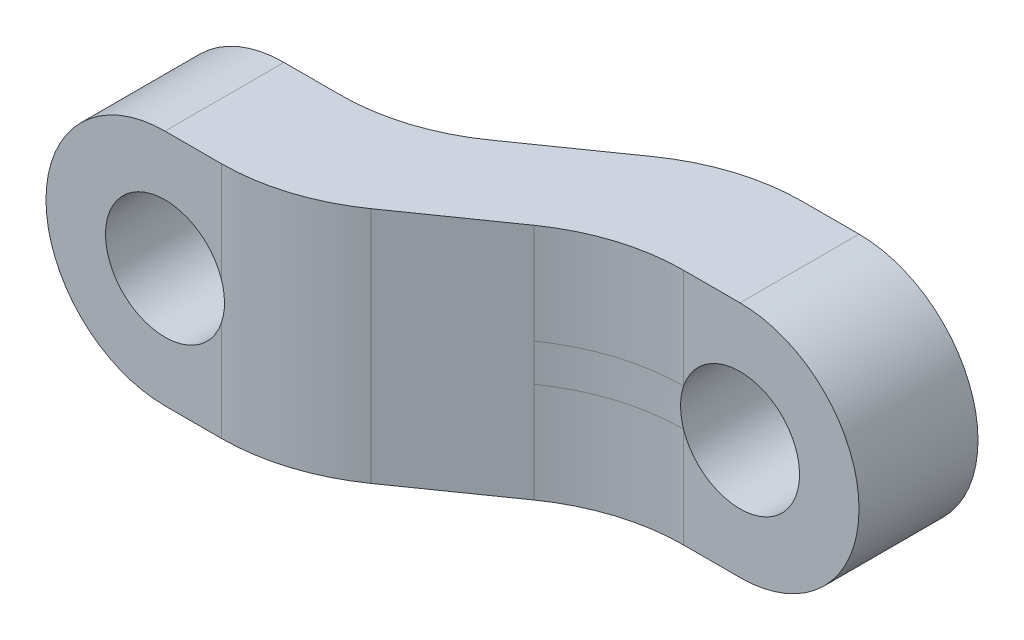
SolidWorks part; units mm, degrees
ref_plane "Front Plane" through (0, 0, 0) normal (0, 0, 1) x (1, 0, 0)
ref_plane "Top Plane" through (0, 0, 0) normal (0, 1, 0) x (1, 0, 0)
ref_plane "Right Plane" through (0, 0, 0) normal (1, 0, 0) x (0, 0, -1)
sketch "Sketch2" plane through (0, 0, 0) normal (0, 0, 1) x (1, 0, 0)
  line L1 (-3, -3) -> (3, -3)
  line L2 (-3, -3) -> (-3, 3)
  line L3 (-3, 3) -> (3, 3)
  line L4 (3, -3) -> (3, 3)
  line L5 (-3, -3) -> (3, 3) construction
  line L6 (-3, 3) -> (3, -3) construction
  circle A0 centre (0, 0) radius 1.5
  circle A1 centre (0, 0) radius 3
  dimension "D1" = 3
  dimension "D2" = 6
  dimension "D3" = 6
sketch "Sketch3" plane through (0, 0, 0) normal (0, 1, 0) x (1, 0, 0)
  line L0 (-1.5, 0) -> (1.5, 0) construction
  line L1 (-6, -1.5) -> (3, -1.5)
  line L2 (-6, -1.5) -> (-6, 1.5)
  line L3 (-6, 1.5) -> (3, 1.5)
  line L4 (3, -1.5) -> (3, 1.5)
  line L5 (-6, -1.5) -> (3, 1.5) construction
  line L6 (-6, 1.5) -> (3, -1.5) construction
  line L7 (-3, 0) -> (3, 0) construction
  line L8 (-3, 0) -> (3, 0) construction
  line L9 (-14, -3.5) -> (-8, -3.5) construction
  line L10 (-14, -5) -> (-5, -5)
  line L11 (-14, -5) -> (-14, -2)
  line L12 (-14, -2) -> (-5, -2)
  line L13 (-5, -5) -> (-5, -2)
  line L14 (-14, -5) -> (-5, -2) construction
  line L15 (-14, -2) -> (-5, -5) construction
  line L16 (-3, 0) -> (-3, -1.5) construction
  line L17 (-8, -3.5) -> (-8, -5) construction
  line L18 (-8, -5) -> (-8, -2) construction
  line L19 (-8, -5) -> (-3, -1.5)
  line L20 (-8, -2) -> (-3, 1.5)
  point P0 (-1.5, 0)
  point P15 (0, 0)
  point P16 (-9.5, -3.5)
  dimension "D1" = 3
  dimension "D2" = 9
  dimension "D3" = 6
  dimension "D4" = 3
  dimension "D5" = 9
  dimension "D6" = 6
  dimension "D7" = 2
  dimension "D8" = 0.5
extrude "Boss-Extrude1" add sketch "Sketch3" along normal blind 3 and the other way blind 3 contours L10 L19 L13 L1 L12 L11 | L13 L19 L1 | L20 L2 L1 L4 L3 | L20 L12 L2 region at (-1.0377, 0, 0.1057) region at (-5.5, 0, 1.75) region at (-9.9623, 0, 3.3943)
sketch "Sketch4" plane through (0, 0, 5) normal (0, 0, 1) x (1, 0, 0)
  line L0 (-14, -3) -> (-14, 3) construction
  line L1 (-14, 3) -> (-8, 3) construction
  line L2 (-14, -3) -> (-8, -3) construction
  line L3 (-8, 3) -> (-14, 3)
  line L4 (-8, 3) -> (-8, -3)
  line L5 (-8, -3) -> (-14, -3)
  line L6 (-14, 3) -> (-14, -3)
  line L7 (-8, 3) -> (-14, -3) construction
  line L8 (-8, -3) -> (-14, 3) construction
  circle A0 centre (-11, 0) radius 3
  circle A1 centre (-11, 0) radius 1.5
  line M5 (-14, 3) -> (-14, -3)
  line M6 (-14, -3) -> (-8, -3)
  dimension "D1" = 6
  dimension "D2" = 3
extrude "Cut-Extrude1" cut sketch "Sketch2" against normal blind 3 and the other way blind 3 contours A1 L4 L3 | A1 L1 L4 | A0 region at (2.3299, -2.3299, 0) region at (2.3299, 2.3299, 0) region at (0, 0, 0)
extrude "Cut-Extrude3" cut sketch "Sketch4" against normal blind 3 and the other way blind 3 contours A0 L6 M6 | A0 L3 M5 | A1 region at (-13.3299, 2.3299, 5) region at (-13.3299, -2.3299, 5) region at (-11, 0, 5)
fillet "Fillet1" radius 5 4 edges at (-8, 0, 5) (-3, 0, 1.5) (-3, 0, -1.5) (-8, 0, 2)
